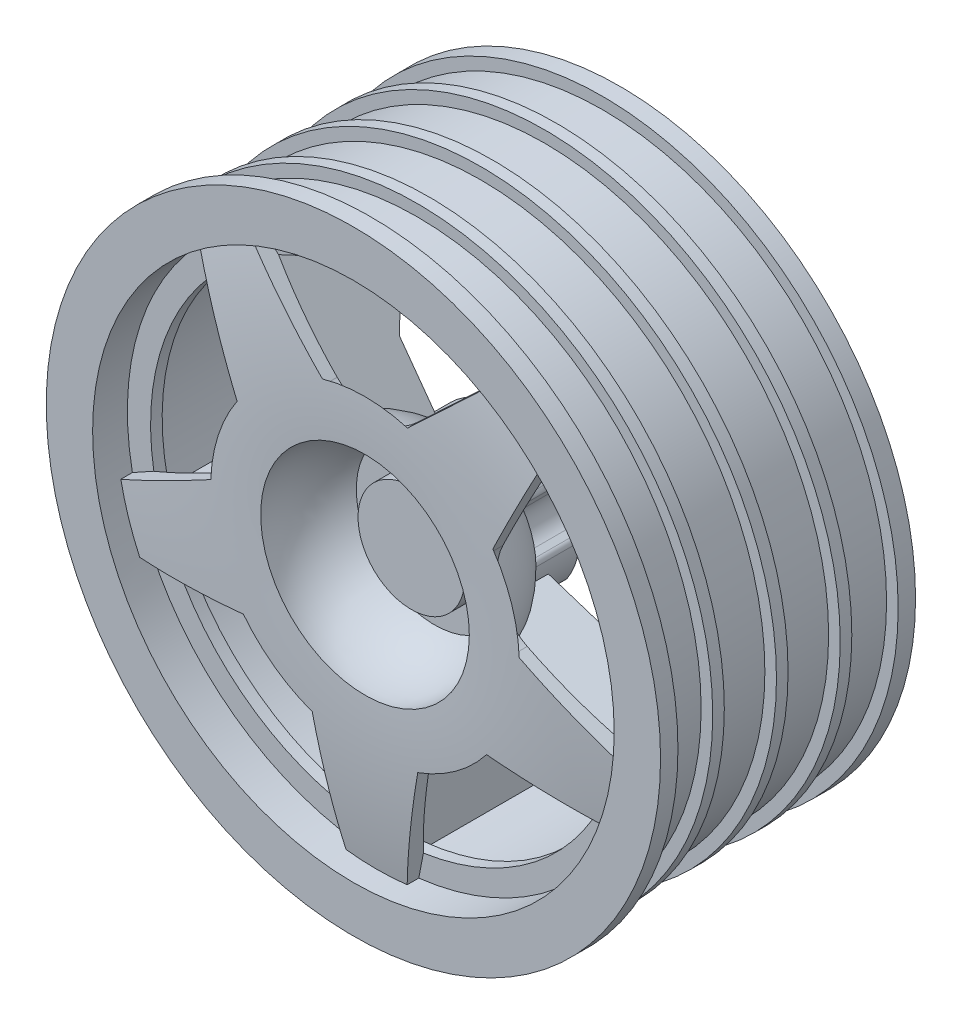
SolidWorks part; units mm, degrees
ref_plane "Front Plane" through (0, 0, 0) normal (0, 0, 1) x (1, 0, 0)
ref_plane "Top Plane" through (0, 0, 0) normal (0, 1, 0) x (1, 0, 0)
ref_plane "Right Plane" through (0, 0, 0) normal (1, 0, 0) x (0, 0, -1)
sketch "Sketch1" plane through (0, 0, 0) normal (1, 0, 0) x (0, 0, -1)
  line L0 (-16.8126, 0) -> (98.1009, 0) construction
  line L1 (0, 0) -> (0, 4.6)
  line L2 (0, 4.6) -> (2, 4.6)
  line L3 (2, 4.6) -> (2, 6.75)
  line L4 (-3, 22.5) -> (-5, 22.5)
  line L5 (-5, 22.5) -> (-5, 26.5)
  line L6 (-5, 26.5) -> (-3.5, 26.5)
  line L7 (-3.5, 26.5) -> (-3.5, 24.5)
  line L8 (-3.5, 24.5) -> (0.5, 24.5)
  line L9 (0.5, 24.5) -> (0.5, 25.5)
  line L10 (0.5, 25.5) -> (1.5, 25.5)
  line L11 (1.5, 25.5) -> (1.5, 24.5)
  line L12 (1.5, 24.5) -> (6, 24.5)
  line L13 (6, 24.5) -> (6, 25.5)
  line L14 (6, 25.5) -> (7, 25.5)
  line L15 (7, 25.5) -> (7, 24.5)
  line L16 (7, 24.5) -> (11.5, 24.5)
  line L17 (11.5, 24.5) -> (11.5, 25.5)
  line L18 (11.5, 25.5) -> (12.5, 25.5)
  line L19 (12.5, 25.5) -> (12.5, 24.5)
  line L20 (12.5, 24.5) -> (16.5, 24.5)
  line L21 (16.5, 24.5) -> (16.5, 25.5)
  line L22 (16.5, 25.5) -> (18, 25.5)
  line L23 (18, 25.5) -> (18, 22.5)
  line L24 (18, 22.5) -> (-1, 22.5)
  line L25 (-1, 22.5) -> (-1, 20.5)
  line L26 (-1, 20.5) -> (-2, 20.5)
  line L27 (0, 0) -> (4, 0)
  line L28 (4, 0) -> (4, 6.75)
  arc A0 (-4, 9) -> (-3, 22.5) centre (58.5258, 11.1555) cw
  arc A1 (2, 6.75) -> (-4, 9) centre (-3.3147, 1.7024) ccw
  arc A2 (-2, 20.5) -> (-3, 10) centre (38.02, 11.3909) ccw
  arc A3 (-3, 10) -> (4, 6.75) centre (-3.7789, -0.841) cw
  point P13 (-3.8662, 15.7771)
  dimension "D1" = 4.6
  dimension "D2" = 2
  dimension "D3" = 6.75
  dimension "D4" = 4
  dimension "D5" = 22.5
  dimension "D6" = 1
  dimension "D7" = 9
  dimension "D8" = 2
  dimension "D9" = 4
  dimension "D10" = 1.5
  dimension "D11" = 2
  dimension "D12" = 4
  dimension "D13" = 1
  dimension "D14" = 1
  dimension "D15" = 1
  dimension "D16" = 4.5
  dimension "D17" = 1
  dimension "D18" = 1
  dimension "D19" = 1
  dimension "D20" = 1
  dimension "D21" = 1
  dimension "D22" = 1
  dimension "D23" = 4
  dimension "D24" = 1
  dimension "D25" = 1.5
  dimension "D26" = 4.5
  dimension "D27" = 19
  dimension "D28" = 2
  dimension "D29" = 1
  dimension "D30" = 1
  dimension "D31" = 1
  dimension "D32" = 4
  dimension "D33" = 6.75
revolve "Revolve1" add sketch "Sketch1" angle 360 about L0
ref_plane "Plane1" through (0, 0, 4) normal (0, 0, 1) x (1, 0, 0)
sketch "Sketch2" plane through (0, 0, 4) normal (0, 0, 1) x (1, 0, 0)
  line L0 (0, -28.9098) -> (0, 27.4133) construction
  line L1 (-11, 19.6278) -> (11, 19.6278)
  line L2 (-11, 19.6278) -> (-3.41, 12.55)
  line L3 (3.41, 12.55) -> (11, 19.6278)
  line L4 (15.2679, 16.5269) -> (10.882, 7.1213)
  line L5 (12.9895, 0.6351) -> (22.0663, -4.3963)
  line L6 (20.4361, -9.4136) -> (10.1354, -8.1488)
  line L7 (4.618, -12.1575) -> (2.6377, -22.3449)
  line L8 (-2.6377, -22.3449) -> (-4.618, -12.1575)
  line L9 (-10.1354, -8.1488) -> (-20.4361, -9.4136)
  line L10 (-22.0663, -4.3963) -> (-12.9895, 0.6351)
  line L11 (-10.882, 7.1213) -> (-15.2679, 16.5269)
  arc A0 (11, 19.6278) -> (-11, 19.6278) centre (0, 0) ccw
  arc A1 (-3.41, 12.55) -> (3.41, 12.55) centre (0, 16.2068) ccw
  arc A2 (-3.41, 12.55) -> (3.41, 12.55) centre (0, 16.2068) ccw
  arc A3 (22.0663, -4.3963) -> (15.2679, 16.5269) centre (0, 0) ccw
  arc A4 (10.882, 7.1213) -> (12.9895, 0.6351) centre (15.4135, 5.0082) ccw
  arc A5 (2.6377, -22.3449) -> (20.4361, -9.4136) centre (0, 0) ccw
  arc A6 (10.1354, -8.1488) -> (4.618, -12.1575) centre (9.5261, -13.1115) ccw
  arc A7 (-20.4361, -9.4136) -> (-2.6377, -22.3449) centre (0, 0) ccw
  arc A8 (-4.618, -12.1575) -> (-10.1354, -8.1488) centre (-9.5261, -13.1115) ccw
  arc A9 (-15.2679, 16.5269) -> (-22.0663, -4.3963) centre (0, 0) ccw
  arc A10 (-12.9895, 0.6351) -> (-10.882, 7.1213) centre (-15.4135, 5.0082) ccw
  point P12 (0, 9.3701)
  point P44 (0, 0)
  dimension "D1" = 45
  dimension "D4" = 5
  dimension "D5" = 5
  dimension "D2" = 11
  dimension "D3" = 94
  dimension "D6" = 5
extrude "Cut-Extrude2" cut sketch "Sketch2" against normal blind 2 contours L8 A8 L9 A7 | L10 A10 L11 A9 | L6 A6 L7 A5 | L1 L0 A0 | L0 L1 A0 | L0 A2 L3 L1 | A1 L0 L1 L2 | L4 A4 L5 A3 region at (-3.7828, 16.4368, 4) region at (3.7828, 16.4368, 4) region at (-4.1625, 20.7832, 4) region at (4.1625, 20.7832, 4) region at (16.8013, 5.4591, 4) region at (10.3838, -14.292, 4) region at (-10.3838, -14.292, 4) region at (-16.8013, 5.4591, 4)
sketch "Sketch3" plane through (0, 0, -4) normal (0, 0, -1) x (-1, 0, 0)
  line L1 (-1.364, 5.5916) -> (-1.7791, 5.9786)
  line L2 (1.7791, 5.9786) -> (1.364, 5.5916)
  line L3 (6.2358, 0.1555) -> (5.7394, 0.4307)
  line L4 (4.8964, 3.0251) -> (5.1363, 3.5395)
  line L5 (2.0749, -5.8825) -> (2.1831, -5.3254)
  line L6 (4.3901, -3.7219) -> (4.9535, -3.7911)
  line L7 (-4.9535, -3.7911) -> (-4.3901, -3.7219)
  line L8 (-2.1831, -5.3254) -> (-2.0749, -5.8825)
  line L9 (-5.1363, 3.5395) -> (-4.8964, 3.0251)
  line L10 (-5.7394, 0.4307) -> (-6.2358, 0.1555)
  arc A0 (-6.4928, -0.3053) -> (-5.4323, -3.5694) centre (0, 0) ccw
  arc A1 (-1.364, 5.5916) -> (1.364, 5.5916) centre (0, 7.0543) ccw
  arc A2 (4.8964, 3.0251) -> (5.7394, 0.4307) centre (6.709, 2.1799) ccw
  arc A3 (4.3901, -3.7219) -> (2.1831, -5.3254) centre (4.1464, -5.707) ccw
  arc A4 (-2.1831, -5.3254) -> (-4.3901, -3.7219) centre (-4.1464, -5.707) ccw
  arc A5 (-5.7394, 0.4307) -> (-4.8964, 3.0251) centre (-6.709, 2.1799) ccw
  arc A6 (-1.716, -6.2694) -> (1.716, -6.2694) centre (0, 0) ccw
  arc A7 (5.4323, -3.5694) -> (6.4928, -0.3053) centre (0, 0) ccw
  arc A8 (5.0734, 4.0634) -> (2.2967, 6.0807) centre (0, 0) ccw
  arc A9 (-2.2967, 6.0807) -> (-5.0734, 4.0634) centre (0, 0) ccw
  arc A10 (-6.2358, 0.1555) -> (-6.4928, -0.3053) centre (-5.9934, -0.2818) ccw
  arc A11 (-4.9535, -3.7911) -> (-5.4323, -3.5694) centre (-5.0144, -3.2948) cw
  arc A12 (-2.0749, -5.8825) -> (-1.716, -6.2694) centre (-1.584, -5.7871) ccw
  arc A13 (2.0749, -5.8825) -> (1.716, -6.2694) centre (1.584, -5.7871) cw
  arc A14 (4.9535, -3.7911) -> (5.4323, -3.5694) centre (5.0144, -3.2948) ccw
  arc A15 (6.2358, 0.1555) -> (6.4928, -0.3053) centre (5.9934, -0.2818) cw
  arc A16 (5.1363, 3.5395) -> (5.0734, 4.0634) centre (4.6831, 3.7508) ccw
  arc A17 (2.2967, 6.0807) -> (1.7791, 5.9786) centre (2.1201, 5.613) ccw
  arc A18 (-2.2967, 6.0807) -> (-1.7791, 5.9786) centre (-2.1201, 5.613) cw
  arc A19 (-5.1363, 3.5395) -> (-5.0734, 4.0634) centre (-4.6831, 3.7508) cw
  point P1 (0, 0)
  point P10 (0, 4.3196)
  point P32 (0, 0)
  point P46 (2, 6.1847)
  point P49 (-2, 6.1847)
  dimension "D1" = 13
  dimension "D5" = 2
  dimension "D7" = 0.5
  dimension "D2" = 2
  dimension "D3" = 2
  dimension "D4" = 94
  dimension "D6" = 5
extrude "Boss-Extrude1" add sketch "Sketch3" along normal blind 4
sketch "Sketch4" plane through (0, 0, -8) normal (0, 0, -1) x (-1, 0, 0)
  circle A0 centre (0, 0) radius 4.6
  dimension "D1" = 9.2
extrude "Boss-Extrude2" add sketch "Sketch4" along normal blind 14
sketch "Sketch6" plane through (0, 0, -22) normal (0, 0, -1) x (-1, 0, 0)
  circle A0 centre (0, 0) radius 2.55
  dimension "D1" = 5.1
extrude "Cut-Extrude3" cut sketch "Sketch6" against normal blind 4
sketch "Sketch7" plane through (0, 0, -18) normal (0, 0, -1) x (-1, 0, 0)
  line L0 (-2, 1.5819) -> (-2, -1.5819)
  line L1 (2, 1.5819) -> (2, -1.5819)
  arc A0 (-2, -1.5819) -> (2, -1.5819) centre (0, 0) ccw
  arc A1 (2, 1.5819) -> (-2, 1.5819) centre (0, 0) ccw
  dimension "D1" = 5.1
  dimension "D2" = 2
  dimension "D3" = 2
extrude "Cut-Extrude4" cut sketch "Sketch7" against normal blind 10
sketch "Sketch8" plane through (0, 0, 0) normal (1, 0, 0) x (0, 0, -1)
  line L0 (-1, -22.7596) -> (10, -22.7596)
  line L1 (-1, -22.5) -> (-1, 22.5) construction
  line L2 (-1, -22.7596) -> (-1, -20.8035)
  line L3 (-1, -20.5) -> (-1, 20.5) construction
  line L4 (-1, -20.8035) -> (-2.1921, -20.8035)
  line L5 (10, -22.7596) -> (10, -19.2557)
  line L6 (10, -19.2557) -> (5.5, -11.7694)
  line L7 (5.5, -11.7694) -> (5.5, -6.2694)
  line L8 (8, -6.2694) -> (4, -6.2694) construction
  line L9 (5.5, -6.2694) -> (3.7923, -6.2694)
  line L16 (3.7923, -6.2694) -> (0.6418, -8.8188)
  line L17 (0.6418, -8.8188) -> (-3.2804, -9.7934)
  line L18 (-3.2804, -9.7934) -> (-3.0342, -16.7901)
  line L19 (-3.0342, -16.7901) -> (-2.1921, -20.8035)
  dimension "D1" = 11
  dimension "D2" = 4.5
  dimension "D3" = 5.5
extrude "Boss-Extrude4" add sketch "Sketch8" along normal mid plane 1
pattern_circular "CirPattern1" count 5 over 360 about axis through (0, 0, 16.8126) along (0, 0, 1) of "Boss-Extrude4"
